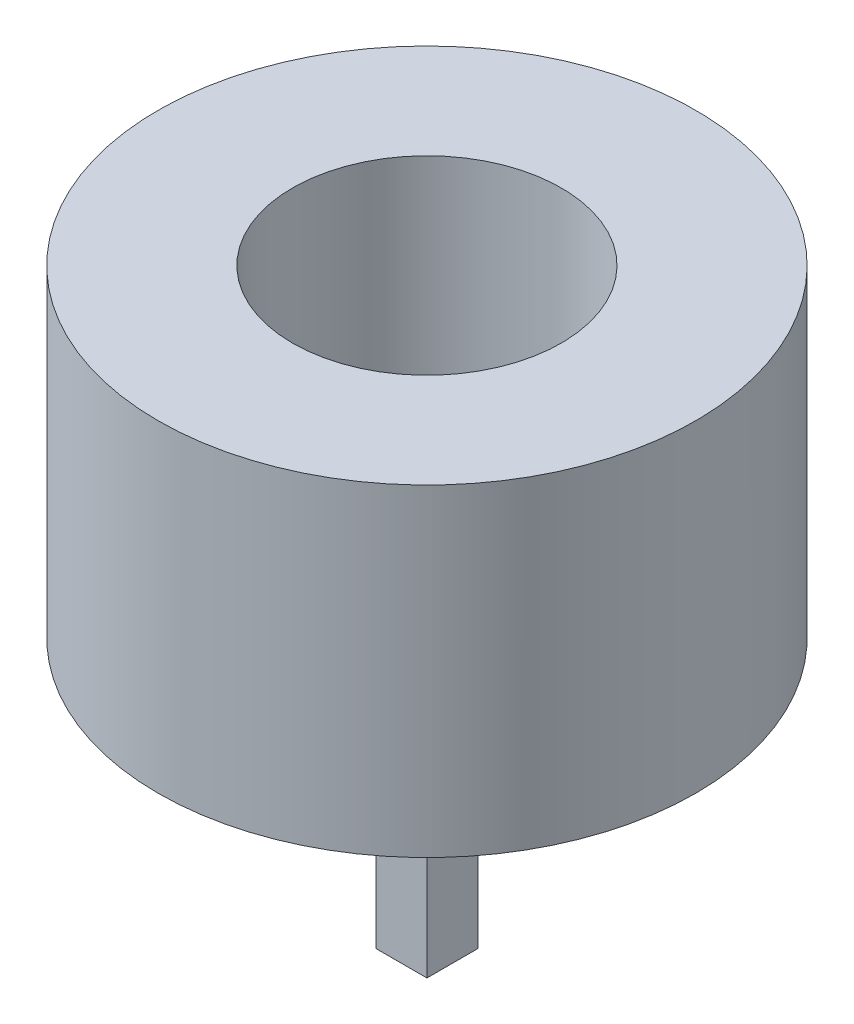
SolidWorks part; units mm, degrees
material "PLA Aero Bambu"
ref_plane "Front Plane" through (0, 0, 0) normal (0, 0, 1) x (1, 0, 0)
ref_plane "Top Plane" through (0, 0, 0) normal (0, 1, 0) x (1, 0, 0)
ref_plane "Right Plane" through (0, 0, 0) normal (1, 0, 0) x (0, 0, -1)
sketch "Sketch1" plane through (0, 0, 0) normal (0, 1, 0) x (1, 0, 0)
  circle A0 centre (0, 0) radius 2.5
  circle A1 centre (0, 0) radius 5
  dimension "D1" = 5
  dimension "D2" = 10
extrude "Boss-Extrude1" add sketch "Sketch1" along normal blind 3 and the other way blind 2
sketch "Sketch2" plane through (0, -2, 0) normal (0, -1, 0) x (1, 0, 0)
  circle A0 centre (0, 0) radius 5
  circle A1 centre (0, 0) radius 5 construction
extrude "Boss-Extrude2" add sketch "Sketch2" along normal blind 1
sketch "Sketch3" plane through (0, -3, 0) normal (0, -1, 0) x (1, 0, 0)
  line L1 (-0.475, 0.475) -> (0.475, 0.475)
  line L2 (-0.475, 0.475) -> (-0.475, -0.475)
  line L3 (-0.475, -0.475) -> (0.475, -0.475)
  line L4 (0.475, 0.475) -> (0.475, -0.475)
  line L5 (-0.475, 0.475) -> (0.475, -0.475) construction
  line L6 (-0.475, -0.475) -> (0.475, 0.475) construction
  point P0 (0, 0)
  dimension "D1" = 0.95
extrude "Boss-Extrude3" add sketch "Sketch3" along normal blind 5
